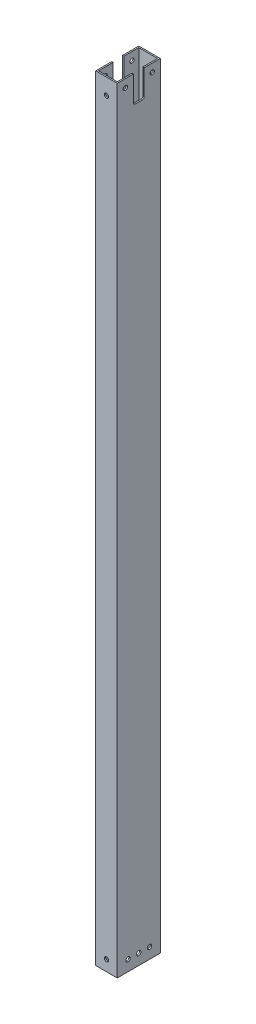
SolidWorks part; units mm, degrees
material "6061-T6 (SS)"
ref_plane "Front" through (0, 0, 0) normal (0, 0, 1) x (1, 0, 0)
ref_plane "Top" through (0, 0, 0) normal (0, 1, 0) x (1, 0, 0)
ref_plane "Right" through (0, 0, 0) normal (1, 0, 0) x (0, 0, -1)
sketch "Sketch1" plane through (0, 0, 0) normal (0, 1, 0) x (1, 0, 0)
  line L1 (12.7, 25.4) -> (-12.7, 25.4)
  line L2 (12.7, 25.4) -> (12.7, -25.4)
  line L3 (12.7, -25.4) -> (-12.7, -25.4)
  line L4 (-12.7, 25.4) -> (-12.7, -25.4)
  line L5 (12.7, 25.4) -> (-12.7, -25.4) construction
  line L6 (12.7, -25.4) -> (-12.7, 25.4) construction
  point P0 (0, 0)
  dimension "D1" = 25.4
  dimension "D2" = 50.8
extrude "Extrude-Thin1" add sketch "Sketch1" along normal blind 914.4 thin thin type one direction reverse wall 1.5875
sketch "Sketch2" plane through (-12.7, 0, 0) normal (-1, 0, 0) x (0, 0, 1)
  line L0 (-25.4, 914.4) -> (25.4, 914.4) construction
  line L1 (-6.35, 914.4) -> (6.35, 914.4)
  line L2 (-6.35, 914.4) -> (-6.35, 884.428)
  line L3 (-4.572, 882.65) -> (4.572, 882.65)
  line L4 (6.35, 914.4) -> (6.35, 884.428)
  line L5 (-25.4, 914.4) -> (-6.35, 882.65) construction
  line L6 (25.4, 914.4) -> (6.35, 882.65) construction
  arc A0 (4.572, 882.65) -> (6.35, 884.428) centre (4.572, 884.428) ccw
  arc A1 (-6.35, 884.428) -> (-4.572, 882.65) centre (-4.572, 884.428) ccw
  dimension "D3" = 1.778
  dimension "D1" = 12.7
  dimension "D2" = 31.75
extrude "Cut-Extrude1" cut sketch "Sketch2" against normal through all
sketch "Sketch5" plane through (0, 0, 25.4) normal (0, 0, 1) x (1, 0, 0)
  line L3 (-12.7, 914.4) -> (12.7, 914.4) construction
  line L4 (-12.7, 0) -> (12.7, 0) construction
  point P0 (0, 895.35)
  point P12 (0, 12.7)
  dimension "D1" = 19.05
  dimension "D2" = 12.7
hole_wizard "#10 Clearance Hole1" positions "Sketch5" profile "Sketch4" hole size "#10" standard "ANSI Inch" end condition through all
sketch "Sketch4" plane through (0, 895.35, 25.4) normal (1, 0, 0) x (0, -1, 0)
  line L0 (0, 0) -> (0, 50.8)
  line L1 (0, 50.8) -> (2.5527, 50.8)
  line L2 (2.5527, 50.8) -> (2.5527, 0)
  line L5 (2.5527, 0) -> (0, 0)
  line L11 (0, -6.35) -> (0, 107.95) construction
  dimension "Thru Hole Dia." = 5.1054
  dimension "Thru Hole Depth" = 50.8
sketch "Sketch8" plane through (-12.7, 0, 0) normal (-1, 0, 0) x (0, 0, 1)
  line L0 (-25.4, 914.4) -> (-15.875, 904.875) construction
  line L3 (25.4, 914.4) -> (15.875, 904.875) construction
  line L5 (-25.4, 914.4) -> (-6.35, 914.4) construction
  line L6 (-25.4, 914.4) -> (-25.4, 0) construction
  line L7 (-12.7, 12.7) -> (12.7, 12.7) construction
  line L9 (-25.4, 0) -> (25.4, 0) construction
  point P0 (15.875, 904.875)
  point P2 (-15.875, 904.875)
  point P20 (-12.7, 12.7)
  point P22 (0, 12.7)
  point P24 (12.7, 12.7)
  point P36 (-15.6268, -1.7491)
  point P37 (0, 0)
  dimension "D1" = 9.525
  dimension "D2" = 9.525
  dimension "D3" = 12.7
  dimension "D4" = 12.7
hole_wizard "#10 Clearance Hole2" positions "Sketch8" profile "Sketch7" hole size "#10" standard "ANSI Inch" end condition through all
sketch "Sketch7" plane through (-12.7, 904.875, 15.875) normal (0, 1, 0) x (0, 0, 1)
  line L0 (0, 0) -> (0, 25.4)
  line L1 (0, 25.4) -> (2.5527, 25.4)
  line L2 (2.5527, 25.4) -> (2.5527, 0)
  line L5 (2.5527, 0) -> (0, 0)
  line L11 (0, -6.35) -> (0, 107.95) construction
  dimension "Thru Hole Dia." = 5.1054
  dimension "Thru Hole Depth" = 25.4
